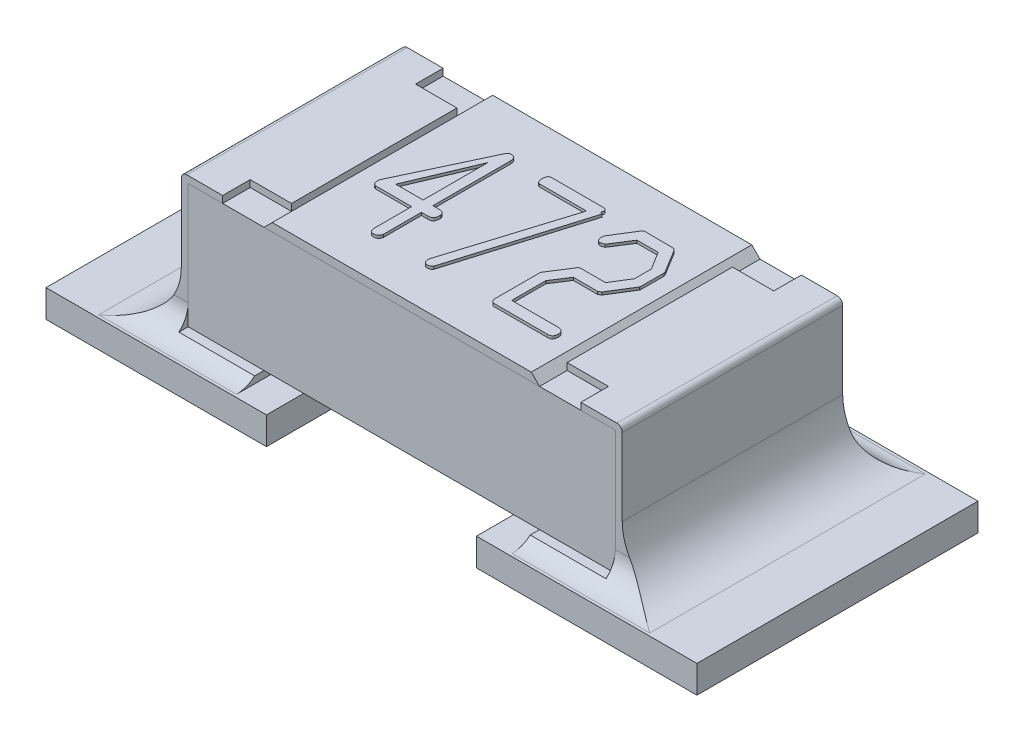
SolidWorks part; units mm, degrees
material "Ceramic Porcelain"
ref_plane "Front Plane" through (0, 0, 0) normal (0, 0, 1) x (1, 0, 0)
ref_plane "Top Plane" through (0, 0, 0) normal (0, 1, 0) x (1, 0, 0)
ref_plane "Right Plane" through (0, 0, 0) normal (1, 0, 0) x (0, 0, -1)
sketch "Sketch1" plane through (0, 0, 0) normal (1, 0, 0) x (0, 0, -1)
  line L0 (0, 55) -> (0, -55) construction
  line L1 (-0.4, 0.575) -> (0.4, 0.575)
  line L2 (-0.4, 0.575) -> (-0.4, 0.125)
  line L3 (-0.4, 0.125) -> (0.4, 0.125)
  line L4 (0.4, 0.575) -> (0.4, 0.125)
  line L5 (55, 0) -> (-55, 0) construction
  dimension "D1" = 0.8
  dimension "D2" = 0.4
  dimension "D3" = 0.45
  dimension "D4" = 0.125
extrude "Boss-Extrude1" add sketch "Sketch1" along normal mid plane 1.55
sketch "Sketch2" plane through (0, 0, 0) normal (0, 0, 1) x (1, 0, 0)
  line L0 (-0.5, 0.6) -> (-0.78, 0.6)
  line L1 (-0.8, 0.58) -> (-0.8, 0.1)
  line L2 (-0.8, 0.1) -> (-0.5, 0.1)
  line L3 (-0.5, 0.1) -> (-0.5, 0.125)
  line L4 (0.775, 0.125) -> (-0.775, 0.125) construction
  line L5 (-0.5, 0.125) -> (-0.775, 0.125)
  line L6 (-0.775, 0.125) -> (-0.775, 0.575)
  line L7 (-0.775, 0.575) -> (-0.5, 0.575)
  line L8 (0.775, 0.575) -> (-0.775, 0.575) construction
  line L9 (-0.5, 0.575) -> (-0.5, 0.6)
  line L11 (0.5, 0.575) -> (0.5, 0.6)
  line L12 (0.5, 0.6) -> (0.78, 0.6)
  line L13 (0.8, 0.58) -> (0.8, 0.1)
  line L14 (0.8, 0.1) -> (0.5, 0.1)
  line L15 (0.5, 0.1) -> (0.5, 0.125)
  line L16 (0.5, 0.125) -> (0.775, 0.125)
  line L17 (0.775, 0.125) -> (0.775, 0.575)
  line L18 (0.775, 0.575) -> (0.5, 0.575)
  arc A0 (0.78, 0.6) -> (0.8, 0.58) centre (0.78, 0.58) cw
  arc A1 (-0.78, 0.6) -> (-0.8, 0.58) centre (-0.78, 0.58) ccw
  point P28 (-0.8, 0.6)
  dimension "D6" = 0.02
  dimension "D1" = 0.025
  dimension "D2" = 0.025
  dimension "D3" = 0.025
  dimension "D4" = 0.3
  dimension "D5" = 0.3
extrude "Boss-Extrude2" add sketch "Sketch2" along normal mid plane 0.8 separate body
sketch "Sketch3" plane through (0, 0.6, 0) normal (0, 1, 0) x (1, 0, 0)
  line L0 (0.5, -0.4) -> (0.5, 0.4) construction
  line L1 (-0.5, 0.4) -> (-0.65, 0.4)
  line L2 (-0.5, 0.4) -> (-0.5, 0.3)
  line L3 (-0.5, 0.3) -> (-0.65, 0.3)
  line L4 (-0.65, 0.4) -> (-0.65, 0.3)
  line L5 (-0.5, -0.4) -> (-0.65, -0.4)
  line L6 (-0.5, -0.4) -> (-0.5, -0.3)
  line L7 (-0.5, -0.3) -> (-0.65, -0.3)
  line L8 (-0.65, -0.4) -> (-0.65, -0.3)
  line L9 (0.5, -0.4) -> (0.65, -0.4)
  line L10 (0.5, -0.4) -> (0.5, -0.3)
  line L11 (0.5, -0.3) -> (0.65, -0.3)
  line L12 (0.65, -0.4) -> (0.65, -0.3)
  line L13 (0.775, -0.4) -> (-0.775, -0.4) construction
  line L15 (0.5, 0.4) -> (0.65, 0.4)
  line L16 (0.5, 0.4) -> (0.5, 0.3)
  line L17 (0.5, 0.3) -> (0.65, 0.3)
  line L18 (0.65, 0.4) -> (0.65, 0.3)
  dimension "D1" = 0.15
  dimension "D2" = 0.1
extrude "Cut-Extrude1" cut sketch "Sketch3" against normal blind 0.025
sketch "Sketch4" plane through (0, 0, 0) normal (0, 0, 1) x (1, 0, 0)
  line L0 (-0.5, 0.575) -> (0.5, 0.575)
  line L1 (0.5, 0.575) -> (0.47, 0.605)
  line L2 (0.47, 0.605) -> (-0.47, 0.605)
  line L3 (-0.47, 0.605) -> (-0.5, 0.575)
  dimension "D1" = 45
  dimension "D2" = 45
  dimension "D3" = 0.03
extrude "Boss-Extrude3" add sketch "Sketch4" along normal mid plane 0.8 separate body
sketch "Sketch6" plane through (0, 0.605, 0) normal (0, 1, 0) x (1, 0, 0)
  line L0 (-0.4, -0.25) -> (0.4, -0.25) construction
  line L1 (0, -0.2777) -> (0, 0.2777) construction
  line L2 (-0.2777, 0) -> (0.2777, 0) construction
  line L3 (-0.47, -0.4) -> (-0.47, 0.4) construction
  line L4 (0.47, 0.4) -> (-0.47, 0.4) construction
  text T0 "<b>472</b>" font "SWMono" height 0.5
  dimension "D1" = 0.8
  dimension "D2" = 0.4
  dimension "D3" = 0.25
extrude "Boss-Extrude4" add sketch "Sketch6" along normal blind 0.01
sketch "Sketch7" plane through (0, 0, 0) normal (0, 1, 0) x (1, 0, 0)
  line L0 (0, -0.2833) -> (0, 0.2833) construction
  line L1 (-0.381, -0.51) -> (-1.181, -0.51)
  line L2 (-0.381, -0.51) -> (-0.381, 0.51)
  line L3 (-0.381, 0.51) -> (-1.181, 0.51)
  line L4 (-1.181, -0.51) -> (-1.181, 0.51)
  line L5 (0.381, -0.51) -> (1.181, -0.51)
  line L6 (0.381, -0.51) -> (0.381, 0.51)
  line L7 (0.381, 0.51) -> (1.181, 0.51)
  line L8 (1.181, -0.51) -> (1.181, 0.51)
  line L9 (-0.2833, 0) -> (0.2833, 0) construction
  dimension "D1" = 0.8
  dimension "D2" = 0.381
  dimension "D3" = 0.381
  dimension "D4" = 1.02
  dimension "D5" = 0.51
extrude "Boss-Extrude5" add sketch "Sketch7" along normal blind 0.1
fillet "Fillet3" radius 0.2 1 edges at (-0.8, 0.1, 0)
fillet "Fillet4" radius 0.2 1 edges at (0.8, 0.1, 0)
fillet "Fillet5" radius 0.1 2 edges at (0.75, 0.1, -0.4) (0.75, 0.1, 0.4)
fillet "Fillet6" radius 0.1 2 edges at (-0.75, 0.1, 0.4) (-0.75, 0.1, -0.4)
